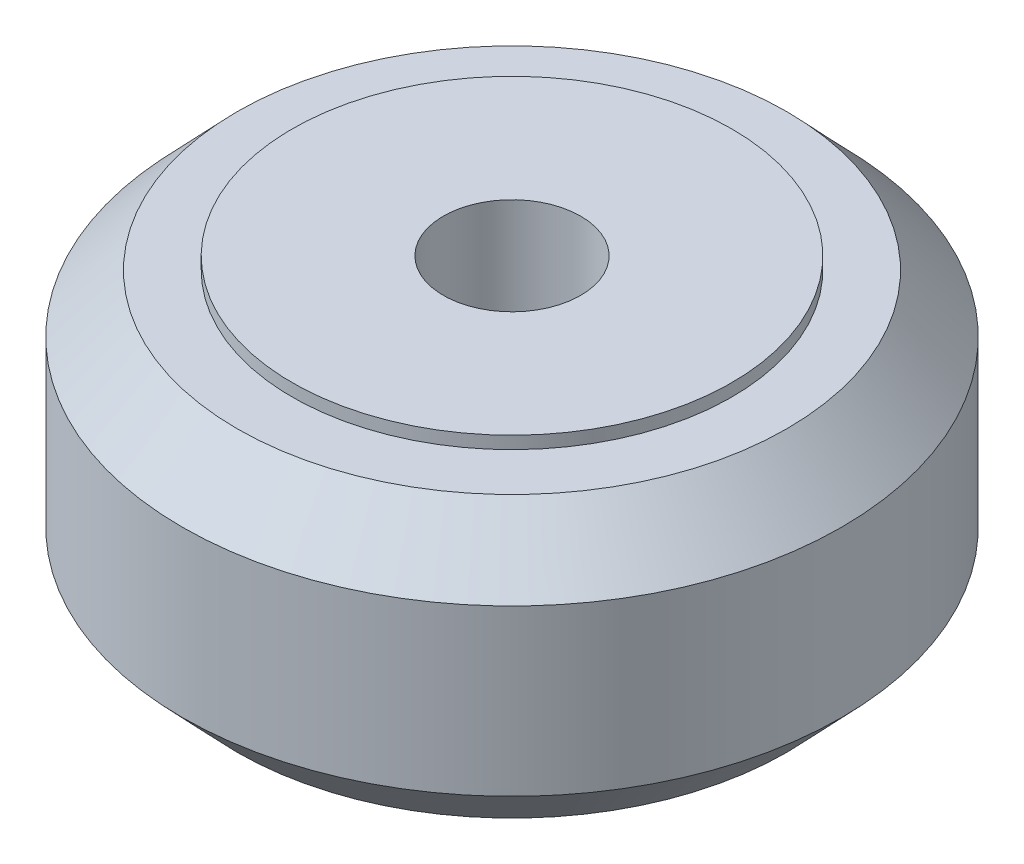
SolidWorks part; units mm, degrees
material "6061 Alloy"
ref_plane "Front Plane" through (0, 0, 0) normal (0, 0, 1) x (1, 0, 0)
ref_plane "Top Plane" through (0, 0, 0) normal (0, 1, 0) x (1, 0, 0)
ref_plane "Right Plane" through (0, 0, 0) normal (1, 0, 0) x (0, 0, -1)
ref_axis "Axis1" through (0, -55, 0) along (0, 1, 0)
sketch "Sketch1" plane through (0, 0, 0) normal (0, 0, 1) x (1, 0, 0)
  line L0 (2.5, -5.555) -> (2.5, 5.555)
  line L1 (2.5, 5.555) -> (8, 5.555)
  line L2 (8, 5.555) -> (8, 5.1)
  line L3 (8, 5.1) -> (10, 5.1)
  line L4 (10, 5.1) -> (12, 3)
  line L5 (0, 0) -> (2.5, 0) construction
  line L6 (10, -5.1) -> (12, -3)
  line L7 (8, -5.1) -> (10, -5.1)
  line L8 (8, -5.555) -> (8, -5.1)
  line L9 (2.5, -5.555) -> (8, -5.555)
  line L10 (12, 3) -> (12, -3)
  line L11 (0, -55) -> (0, 55) construction
  point P2 (2.5, 0)
  point P14 (46.7724, 17.601)
  point P17 (1.2056, 25.4264)
  point P18 (7.1398, 23.4216)
  point P19 (4.2529, 23.181)
  point P20 (9.8663, 19.813)
  point P21 (7.5407, 19.9734)
  point P22 (7.22, 21.5772)
  point P23 (12, 3.0296)
  point P24 (9.4899, 5.1)
  point P25 (12, 3.1266)
  point P26 (9.1199, 5.1)
  dimension "D1" = 12
  dimension "D2" = 11.11
  dimension "D3" = 10.2
  dimension "D4" = 8
  dimension "D5" = 6
  dimension "D6" = 2
  dimension "D7" = 2.5
revolve "Revolve1" add sketch "Sketch1" angle 360 about axis through (0, -55, 0) along (0, 1, 0)
